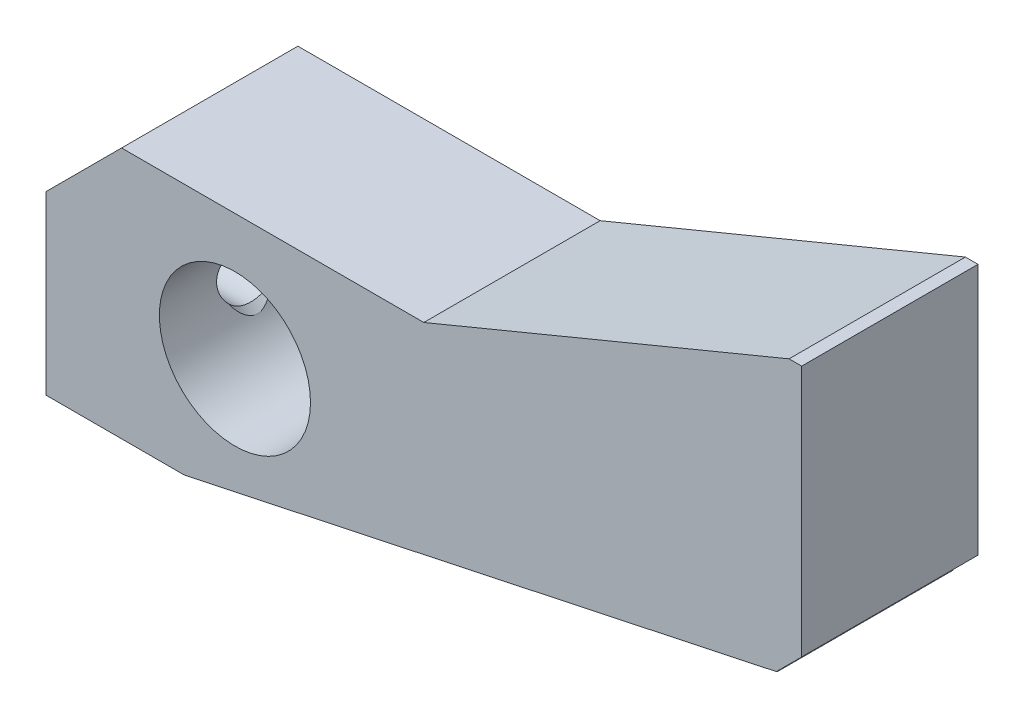
SolidWorks part; units mm, degrees
ref_plane "Front Plane" through (0, 0, 0) normal (0, 0, 1) x (1, 0, 0)
ref_plane "Top Plane" through (0, 0, 0) normal (0, 1, 0) x (1, 0, 0)
ref_plane "Right Plane" through (0, 0, 0) normal (1, 0, 0) x (0, 0, -1)
ref_plane "Plane1" through (0, 0, 0) normal (0, 0, 1) x (1, 0, 0)
sketch "Sketch1" plane through (0, 0, 0) normal (0, 0, 1) x (1, 0, 0)
  line L0 (0, 25) -> (0, 18)
  line L1 (0, 18) -> (5.5, 18)
  line L2 (5.5, 18) -> (29.0232, 23)
  line L3 (29.0232, 23) -> (29, 23)
  line L4 (29, 23) -> (30, 24)
  line L5 (30, 24) -> (30, 34)
  line L6 (30, 34) -> (29.5, 34)
  line L7 (29.5, 34) -> (15, 28)
  line L8 (15, 28) -> (3, 28)
  line L9 (3, 28) -> (0, 25)
extrude "Boss-Extrude1" add sketch "Sketch1" against normal blind 3.5 and the other way blind 3.5
ref_plane "Plane2" through (0, 0, 0) normal (0, 0, 1) x (1, 0, 0)
sketch "Sketch2" plane through (0, 0, 0) normal (0, 0, 1) x (1, 0, 0)
  circle A0 centre (7.5, 23) radius 3
extrude "Cut-Extrude1" cut sketch "Sketch2" against normal blind 3.5 and the other way blind 3.5
ref_plane "Plane3" through (0, 0, 0) normal (0, 0, 1) x (1, 0, 0)
sketch "Sketch3" plane through (0, 0, 0) normal (0, 0, 1) x (1, 0, 0)
  line L0 (4.9019, 23) -> (4.9019, 21.5)
  line L1 (4.9019, 21.5) -> (4.6314, 21.7705)
  line L2 (4.6314, 21.7705) -> (0.2705, 21.7705)
  line L3 (0.2705, 21.7705) -> (0, 21.5)
  line L4 (0, 21.5) -> (0, 23)
  line L5 (0, 23) -> (4.9019, 23)
  line L6 (0, 23) -> (4.9019, 23) construction
revolve "Cut-Revolve1" cut sketch "Sketch3" angle 360 about L6 reverse direction yes
cosmetic thread "Cosmetic Thread1" parameters "D1"=4.6314, "D2"=3
ref_plane "Plane4" through (0, 0, 0) normal (0, 0, 1) x (1, 0, 0)
sketch "Sketch4" plane through (0, 0, 0) normal (0, 0, 1) x (1, 0, 0)
  line L0 (22.9557, 25.7997) -> (25.401, 26.3195)
  line L1 (25.401, 26.3195) -> (26.0857, 23.0985)
  line L2 (26.0857, 23.0985) -> (27.9511, 21.8871)
  line L3 (27.9511, 21.8871) -> (23.9673, 21.0403)
  line L4 (23.9673, 21.0403) -> (22.9557, 25.7997)
  line L5 (23.9673, 21.0403) -> (22.9557, 25.7997) construction
revolve "Cut-Revolve2" cut sketch "Sketch4" angle 360 about L5 reverse direction yes
